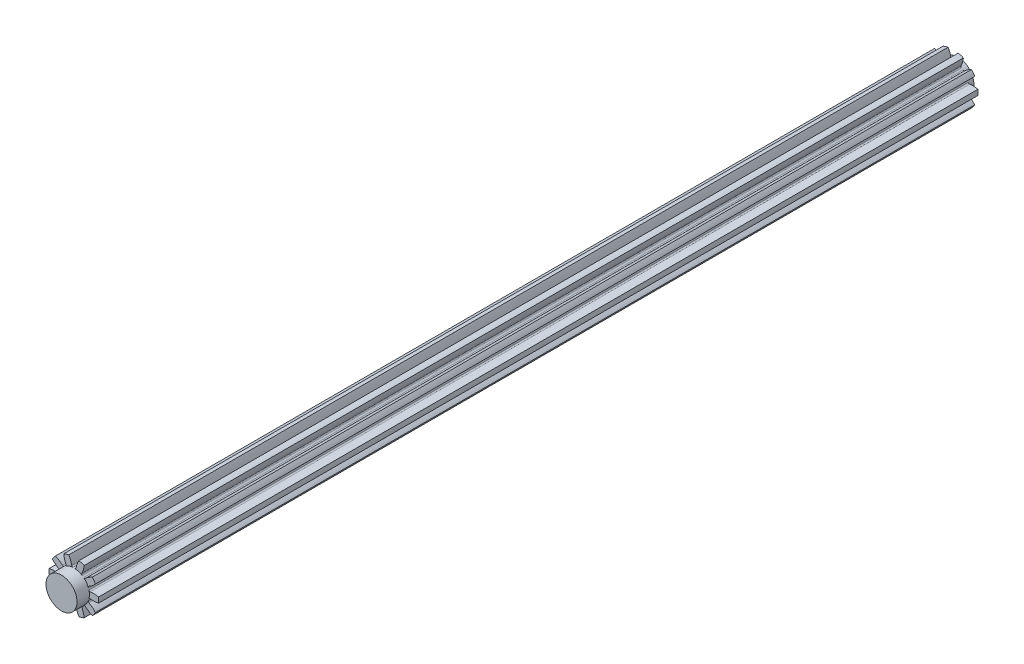
SolidWorks part; units mm, degrees
ref_plane "Front Plane" through (0, 0, 0) normal (0, 0, 1) x (1, 0, 0)
ref_plane "Top Plane" through (0, 0, 0) normal (0, 1, 0) x (1, 0, 0)
ref_plane "Right Plane" through (0, 0, 0) normal (1, 0, 0) x (0, 0, -1)
sketch "Sketch1" plane through (0, 0, 0) normal (0, 0, 1) x (1, 0, 0)
  circle A0 centre (0, 0) radius 10
  circle A1 centre (0, 0) radius 12
  circle A2 centre (0, 0) radius 7.5
  dimension "D1" = 20
  dimension "D2" = 24
  dimension "D3" = 4.5
extrude "Boss-Extrude1" add sketch "Sketch1" along normal mid plane 425 contours A1
sketch "Sketch2" plane through (0, 0, 0) normal (0, 0, 1) x (1, 0, 0)
  line L0 (0, 0) -> (0, 12) construction
  line L1 (-1.5643, 9.8769) -> (1.5643, 9.8769) construction
  line L2 (-0.9691, 7.4371) -> (0, 0) construction
  line L3 (0, 5.5789) -> (-2.6051, 12.7363) construction
  line L4 (0, 0) -> (3.7082, 11.4127) construction
  line L5 (1.5643, 9.8769) -> (4.5399, 8.9101) construction
  circle A0 centre (0, 0) radius 12 construction
  arc A1 (-3.0254, 12.6431) -> (-0.9691, 7.4371) centre (-12.3373, 5.9558) cw
  arc A2 (3.0254, 12.6431) -> (0.9691, 7.4371) centre (12.3373, 5.9558) ccw
  circle A3 centre (0, 0) radius 7.5 construction
  arc A4 (0.9691, 7.4371) -> (-0.9691, 7.4371) centre (0, 0) ccw
  circle A5 centre (0, 0) radius 12 construction
  circle A6 centre (0, 0) radius 10 construction
  circle A7 centre (0, 0) radius 13
  arc A8 (3.0254, 12.6431) -> (-3.0254, 12.6431) centre (0, 0) ccw
  dimension "D2" = 1.9081
  dimension "D3" = 20
  dimension "D4" = 18
extrude "Cut-Extrude1" cut sketch "Sketch2" against normal through all both and the other way through all
fillet "Fillet1" radius 0.6 1 edges at (-0.9691, 7.4371, 0) type face fillet first side face at (-1.5984, 9.6298, 0) second side face at (0, 7.4686, 0)
fillet "Fillet2" radius 0.6 1 edges at (0.9691, 7.4371, 0) type face fillet first side face at (1.5984, 9.6298, 0) second side face at (0.2709, 7.4788, 0)
sketch "Sketch3" plane through (0, 0, -212.5) normal (0, 0, -1) x (-1, 0, 0)
pattern_circular "CirPattern2" count 10 over 360 about axis through (0, 0, 212.5) along (0, 0, 1) of "Cut-Extrude1", "Fillet1", "Fillet2"
sketch "Sketch4" plane through (0, 0, -212.5) normal (0, 0, -1) x (-1, 0, 0)
  circle A0 centre (0, 0) radius 7.5
  circle A1 centre (0, 0) radius 3
  dimension "D1" = 6
extrude "Boss-Extrude2" add sketch "Sketch4" along normal mid plane 5 contours A0 | A1
sketch "Sketch5" plane through (0, 0, -212.5) normal (0, 0, -1) x (-1, 0, 0)
  circle A0 centre (0, 0) radius 3
extrude "Cut-Extrude2" cut sketch "Sketch5" against normal blind 32 and the other way through all
sketch "Sketch6" plane through (0, 0, 212.5) normal (0, 0, 1) x (1, 0, 0)
  circle A0 centre (0, 0) radius 7.5
  dimension "D1" = 15
extrude "Boss-Extrude3" add sketch "Sketch6" along normal mid plane 12
equation "\"Module\"= 2mm"
equation "\"Number of Teeth\"= 10"
equation "\"D1@Sketch1\"=\"Module\" * \"Number of Teeth\""
equation "\"D2@Sketch1\"=(\"Number of Teeth\" + 2) * \"Module\""
equation "\"D3@Sketch1\"=\"Module\" * if( \"Module\" = > 1.25, 2.25, 2.4)"
equation "\"D4@Sketch2\"=180 / \"Number of Teeth\""
equation "\"D1@Fillet1\"=0.3 * \"Module\""
